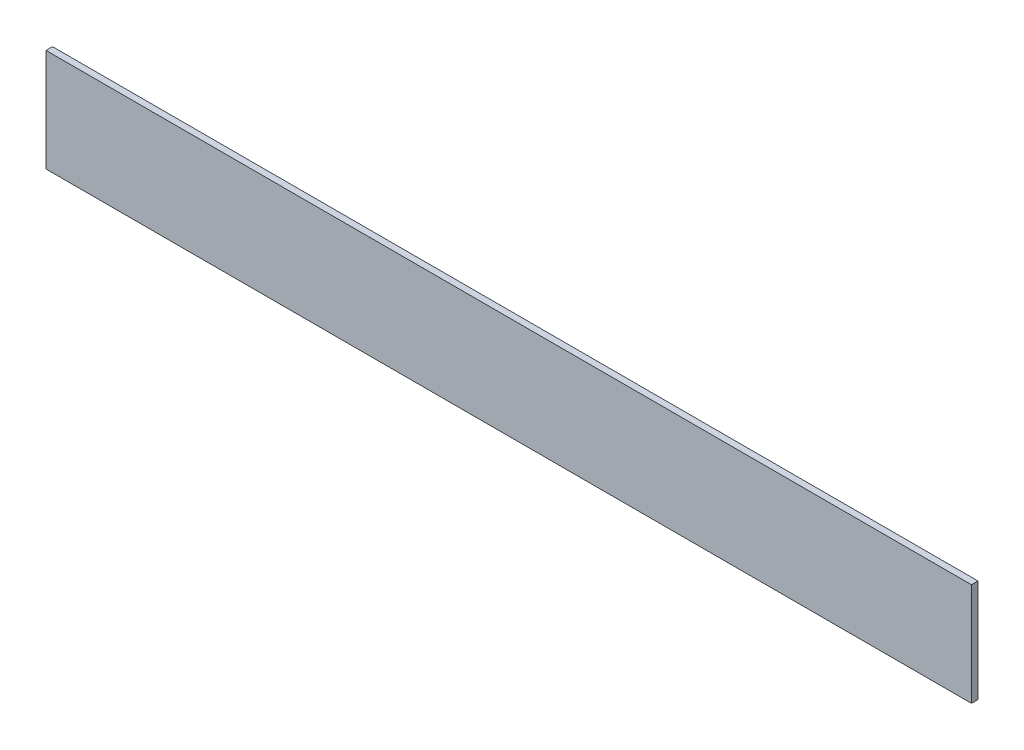
SolidWorks part; units mm, degrees
material "6061-T6 (SS)"
ref_plane "X-Y Datum" through (0, 0, 0) normal (0, 0, 1) x (1, 0, 0)
ref_plane "X-Z Datum" through (0, 0, 0) normal (0, 1, 0) x (1, 0, 0)
ref_plane "Y-Z Datum" through (0, 0, 0) normal (1, 0, 0) x (0, 0, -1)
sketch "Sketch1" plane through (0, 0, 0) normal (0, 0, 1) x (1, 0, 0)
  line L1 (-225.425, -25.019) -> (225.425, -25.019)
  line L2 (-225.425, -25.019) -> (-225.425, 25.019)
  line L3 (-225.425, 25.019) -> (225.425, 25.019)
  line L4 (225.425, -25.019) -> (225.425, 25.019)
  line L5 (-225.425, -25.019) -> (225.425, 25.019) construction
  line L6 (-225.425, 25.019) -> (225.425, -25.019) construction
  point P0 (0, 0)
  dimension "D1" = 450.85
  dimension "D2" = 50.038
extrude "Boss-Extrude1" add sketch "Sketch1" along normal blind 3.175
